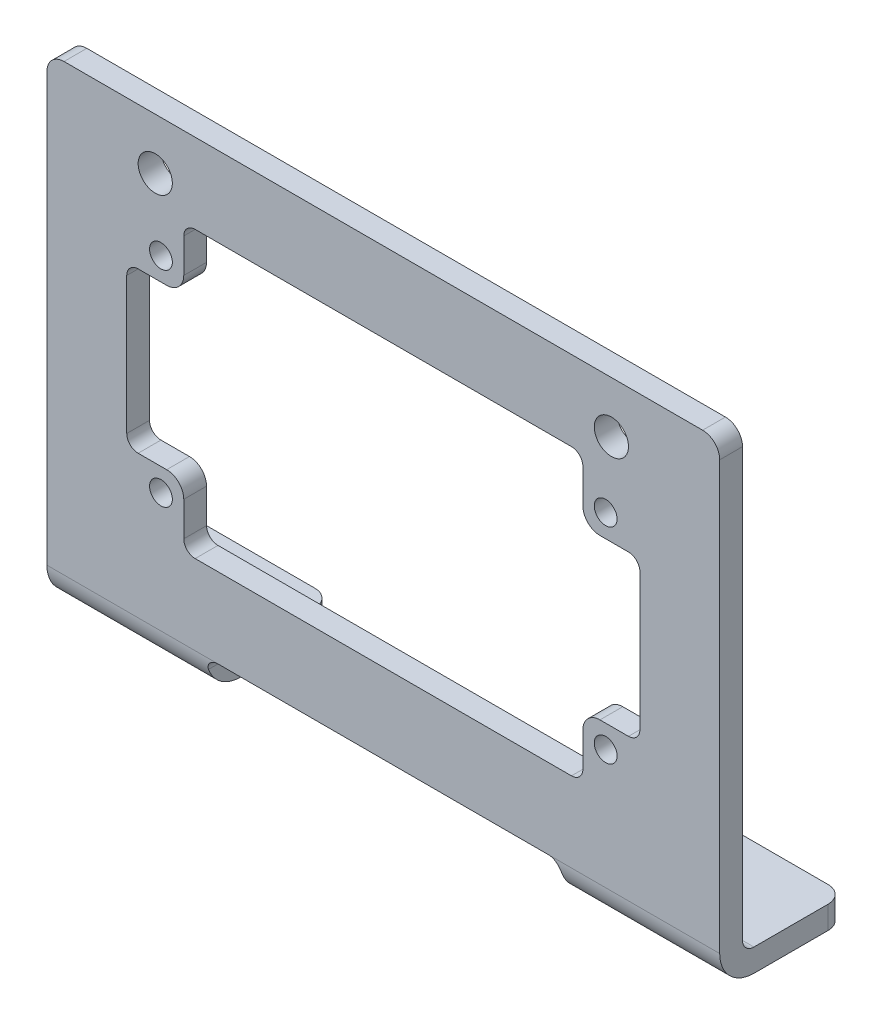
SolidWorks part; units mm, degrees
ref_plane "Front Plane" through (0, 0, 0) normal (0, 0, 1) x (1, 0, 0)
ref_plane "Top Plane" through (0, 0, 0) normal (0, 1, 0) x (1, 0, 0)
ref_plane "Right Plane" through (0, 0, 0) normal (1, 0, 0) x (0, 0, -1)
sketch "Sketch1" plane through (0, 0, 0) normal (0, 0, 1) x (1, 0, 0)
  line L0 (0, -55) -> (0, 55) construction
  line L1 (29.5, -21) -> (-29.5, -21) construction
  line L2 (29.5, -21) -> (29.5, 21) construction
  line L3 (29.5, 21) -> (-29.5, 21) construction
  line L4 (-29.5, -21) -> (-29.5, 21) construction
  line L5 (29.5, -21) -> (-29.5, 21) construction
  line L6 (29.5, 21) -> (-29.5, -21) construction
  line L11 (15.5, -18) -> (-15.5, -18) construction
  line L12 (15.5, -18) -> (15.5, -21) construction
  line L13 (15.5, -21) -> (-15.5, -21) construction
  line L14 (-15.5, -18) -> (-15.5, -21) construction
  line L15 (15.5, -18) -> (-15.5, -21) construction
  line L16 (15.5, -21) -> (-15.5, -18) construction
  line L17 (-22.5, 8.5) -> (-17.5, 8.5)
  line L18 (22.5, 14) -> (-22.5, 14) construction
  line L19 (22.5, 14) -> (22.5, -11) construction
  line L20 (22.5, -11) -> (-22.5, -11) construction
  line L21 (-22.5, 14) -> (-22.5, -11) construction
  line L22 (22.5, 14) -> (-22.5, -11) construction
  line L23 (22.5, -11) -> (-22.5, 14) construction
  line L24 (-17.5, 8.5) -> (-17.5, 14)
  line L25 (-5.0155, 1.5) -> (4.7745, 1.5) construction
  line L26 (-22.5, -5.5) -> (-17.5, -5.5)
  line L27 (-17.5, -5.5) -> (-17.5, -11)
  line L28 (-17.5, 14) -> (17.5, 14)
  line L29 (-22.5, 8.5) -> (-22.5, -5.5)
  line L30 (-17.5, -11) -> (17.5, -11)
  line L31 (-15.5, -18) -> (15.5, -18)
  line L32 (-15.5, -21) -> (-29.5, -21)
  line L33 (-29.5, -21) -> (-29.5, 21)
  line L34 (-29.5, 21) -> (29.5, 21)
  line L35 (-15.5, -18) -> (-15.5, -21)
  line L36 (5.0155, 1.5) -> (-4.7745, 1.5) construction
  line L37 (-22.5, -11) -> (22.5, 14) construction
  line L38 (-22.5, 14) -> (22.5, -11) construction
  line L39 (22.5, 14) -> (22.5, -11) construction
  line L40 (-15.5, -21) -> (15.5, -18) construction
  line L41 (-15.5, -18) -> (15.5, -21) construction
  line L42 (15.5, -18) -> (15.5, -21) construction
  line L43 (-29.5, 21) -> (29.5, -21) construction
  line L44 (-29.5, -21) -> (29.5, 21) construction
  line L45 (29.5, -21) -> (29.5, 21) construction
  line L46 (15.5, -18) -> (15.5, -21)
  line L47 (29.5, -21) -> (29.5, 21)
  line L48 (15.5, -21) -> (29.5, -21)
  line L49 (22.5, 8.5) -> (22.5, -5.5)
  line L50 (17.5, -5.5) -> (17.5, -11)
  line L51 (22.5, -5.5) -> (17.5, -5.5)
  line L52 (17.5, 8.5) -> (17.5, 14)
  line L53 (22.5, 8.5) -> (17.5, 8.5)
  circle A0 centre (-19.5, 10.5) radius 1
  circle A1 centre (-20, 16.5) radius 1.5
  circle A2 centre (-19.5, -7.5) radius 1
  circle A3 centre (19.5, -7.5) radius 1
  circle A4 centre (20, 16.5) radius 1.5
  circle A5 centre (19.5, 10.5) radius 1
  point P0 (0, 0)
  point P7 (0, -19.5)
  point P15 (0, 1.5)
  point P36 (0, -18)
  point P44 (0, 21)
  point P45 (0, -11)
  point P48 (0, 14)
  point P50 (0, 0)
  point P51 (0, 0)
  point P52 (0, 0)
  dimension "D12" = 2
  dimension "D14" = 3
  dimension "D1" = 42
  dimension "D2" = 59
  dimension "D3" = 31
  dimension "D4" = 3
  dimension "D5" = 7
  dimension "D6" = 7
  dimension "D7" = 7
  dimension "D8" = 5
  dimension "D9" = 5.5
  dimension "D10" = 10
  dimension "D11" = 10.5
  dimension "D13" = 9.5
  dimension "D15" = 4.5
extrude "Boss-Extrude1" add sketch "Sketch1" along normal blind 2
sketch "Sketch4" plane through (0, -21, 0) normal (0, -1, 0) x (1, 0, 0)
  line L0 (-15.5, 2) -> (-15.5, 0) construction
  line L1 (-29.5, 2) -> (-15.5, 2) construction
  line L2 (-29.5, 2) -> (-29.5, 0) construction
  line L3 (-15.5, 2) -> (-15.5, 0)
  line L4 (-29.5, 2) -> (-15.5, 2)
  line L5 (-29.5, 2) -> (-29.5, 0)
  line L6 (-29.5, 0) -> (-29.5, -9)
  line L7 (-29.5, -9) -> (-15.5, -9)
  line L8 (-15.5, -9) -> (-15.5, 0)
  line L9 (0, -55) -> (0, 55) construction
  line L10 (15.5, -9) -> (15.5, 0)
  line L11 (29.5, -9) -> (15.5, -9)
  line L12 (29.5, 0) -> (29.5, -9)
  line L13 (29.5, 2) -> (29.5, 0)
  line L14 (29.5, 2) -> (15.5, 2)
  line L15 (15.5, 2) -> (15.5, 0)
  circle A0 centre (-20, -4) radius 1.5
  circle A1 centre (20, -4) radius 1.5
  dimension "D4" = 3
  dimension "D1" = 11
  dimension "D2" = 4.5
  dimension "D3" = 5
extrude "Boss-Extrude2" add sketch "Sketch4" against normal blind 2
fillet "Fillet2" radius 1.5 10 edges at (-29.5, -20, -9) (15.5, -20, -9) (-15.5, -20, -9) (29.5, -20, -9) (17.5, -5.5, 1) (-17.5, -5.5, 1) (-17.5, 8.5, 1) (17.5, 8.5, 1) (-29.5, 21, 1) (29.5, 21, 1)
fillet "Fillet3" radius 1 10 edges at (15.5, -18, 1) (-15.5, -18, 1) (-22.5, 8.5, 1) (-17.5, 14, 1) (-22.5, -5.5, 1) (-17.5, -11, 1) (17.5, -11, 1) (17.5, 14, 1) (22.5, 8.5, 1) (22.5, -5.5, 1)
fillet "Fillet4" radius 1 2 edges at (-22.5, -19, 0) (22.5, -19, 0)
fillet "Fillet5" radius 3 2 edges at (22.5, -21, 2) (-22.5, -21, 2)
